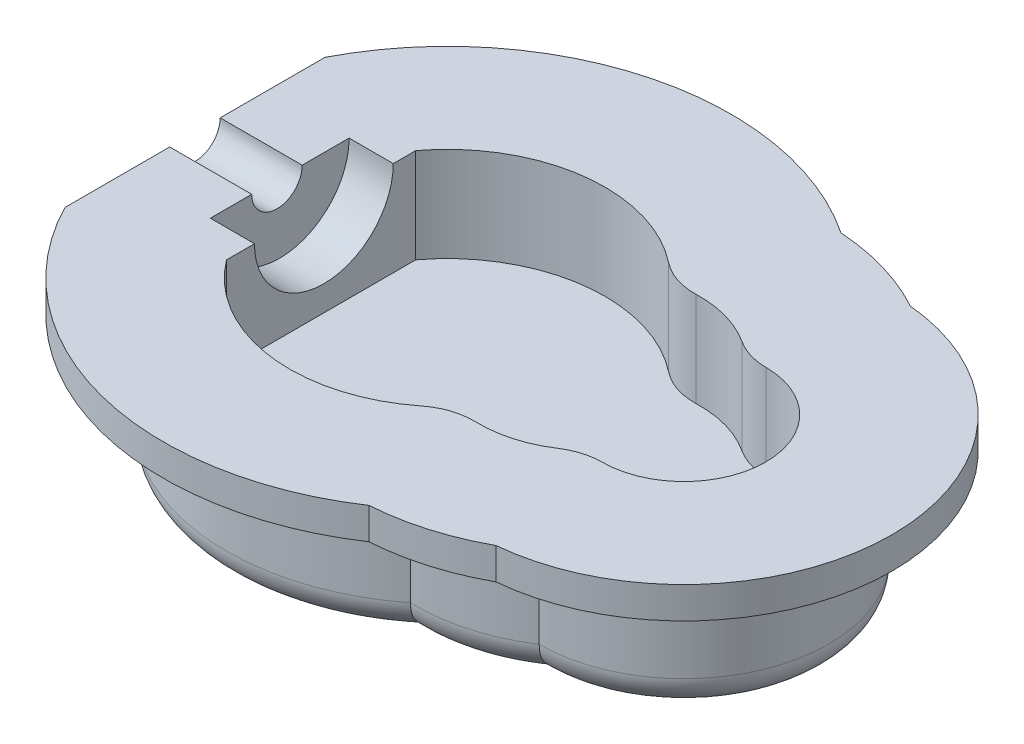
SolidWorks part; units mm, degrees
ref_plane "Front Plane" through (0, 0, 0) normal (0, 0, 1) x (1, 0, 0)
ref_plane "Top Plane" through (0, 0, 0) normal (0, 1, 0) x (1, 0, 0)
ref_plane "Right Plane" through (0, 0, 0) normal (1, 0, 0) x (0, 0, -1)
sketch "Sketch1" plane through (0, 0, 0) normal (0, 1, 0) x (1, 0, 0)
  line L0 (-2125.8372, 0) -> (2252.6955, 0) construction
  line L5 (-57.5, -15) -> (-57.5, 15)
  line L7 (-67.5, -18.0278) -> (-67.5, 18.0278)
  circle A1 centre (0, 0) radius 11
  circle A2 centre (-15, 0) radius 7.5 construction
  circle A3 centre (-37.5, 0) radius 15 construction
  circle A4 centre (0, 0) radius 7.5 construction
  circle A5 centre (-37.5, 0) radius 4
  circle A6 centre (-15, 0) radius 4
  arc A10 (-22.0238, 19.6338) -> (-57.5, 15) centre (-37.5, 0) ccw
  arc A11 (-15.5303, -17.492) -> (-5.4068, -14.6363) centre (-15, 0) ccw
  arc A12 (0.0424, -12.9999) -> (0.0424, 12.9999) centre (0, 0) ccw
  arc A13 (-57.5, -15) -> (-22.0238, -19.6338) centre (-37.5, 0) ccw
  circle A14 centre (-15, 0) radius 17.5 construction
  circle A15 centre (-37.5, 0) radius 25 construction
  circle A16 centre (0, 0) radius 13 construction
  arc A17 (-5.4068, 14.6363) -> (-15.5303, 17.492) centre (-15, 0) ccw
  arc A18 (0.0424, -12.9999) -> (-5.4068, -14.6363) centre (0.075, -22.9999) ccw
  arc A19 (0.0424, 12.9999) -> (-5.4068, 14.6363) centre (0.075, 22.9999) cw
  arc A20 (-15.5303, 17.492) -> (-22.0238, 19.6338) centre (-15.8333, 27.4874) cw
  arc A21 (-15.5303, -17.492) -> (-22.0238, -19.6338) centre (-15.8333, -27.4874) ccw
  arc A31 (0.075, -22.9999) -> (0.075, 22.9999) centre (0, 0) ccw
  arc A32 (0.075, 22.9999) -> (0.075, 22.9999) centre (0.075, 22.9999) cw
  arc A33 (0.075, 22.9999) -> (-15.8333, 27.4874) centre (-15, 0) ccw
  arc A34 (-15.8333, 27.4874) -> (-15.8333, 27.4874) centre (-15.8333, 27.4874) cw
  arc A35 (-15.8333, 27.4874) -> (-67.5, 18.0278) centre (-37.5, 0) ccw
  arc A36 (-67.5, -18.0278) -> (-15.8333, -27.4874) centre (-37.5, 0) ccw
  arc A37 (-15.8333, -27.4874) -> (-15.8333, -27.4874) centre (-15.8333, -27.4874) ccw
  arc A38 (-15.8333, -27.4874) -> (0.075, -22.9999) centre (-15, 0) ccw
  arc A39 (0.075, -22.9999) -> (0.075, -22.9999) centre (0.075, -22.9999) ccw
  point P7 (1088.1233, 0)
  point P9 (919.1687, 0)
  point P19 (991.1425, 0)
  point P22 (1072.1233, 0)
  point P24 (1042.1233, 0)
  point P33 (-2.925, 12.6667)
  dimension "D1" = 30
  dimension "D2" = 22
  dimension "D4" = 15
  dimension "D5" = 15
  dimension "D6" = 8
  dimension "D3" = 8
  dimension "D7" = 10
  dimension "D8" = 10
  dimension "D11" = 10
  dimension "D9" = 2
  dimension "D10" = 30
  dimension "D12" = 10
extrude "Boss-Extrude1" add sketch "Sketch1" along normal blind 10 contours A21 A11 A18 A12 A19 A17 A20 A10 L5 A13 A5 A1 A6 | A5 | A6 | A1 region at (-31.9057, 0, 0) region at (0, 0, 0) region at (-15, 0, 0) region at (-37.5, 0, 0)
extrude "Boss-Extrude2" add sketch "Sketch1<3>" along normal blind 20 contours A36 A11 A21 A13 L5 A10 A20 A17 A19 A12 A18 region at (-66.3559, 0, 0)
sketch "Sketch1<3>" plane through (0, 0, 0) normal (0, 1, 0) x (1, 0, 0) same geometry as "Sketch1"
sketch "Sketch2" plane through (0, 20, 0) normal (0, 1, 0) x (1, 0, 0)
  line L0 (-57.5, -15) -> (-57.5, 15) construction
  line L1 (-57.5, -15) -> (-57.5, 15)
  line L2 (-77.5, -20.6155) -> (-77.5, 20.6155)
  arc A0 (-57.5, -15) -> (-22.0238, -19.6338) centre (-37.5, 0) ccw construction
  arc A1 (-15.5303, -17.492) -> (-22.0238, -19.6338) centre (-15.8333, -27.4874) ccw construction
  arc A2 (-15.5303, -17.492) -> (-5.4068, -14.6363) centre (-15, 0) ccw construction
  arc A3 (0.0424, -12.9999) -> (-5.4068, -14.6363) centre (0.075, -22.9999) ccw construction
  arc A4 (0.0424, -12.9999) -> (0.0424, 12.9999) centre (0, 0) ccw construction
  arc A5 (-5.4068, 14.6363) -> (0.0424, 12.9999) centre (0.075, 22.9999) ccw construction
  arc A6 (-5.4068, 14.6363) -> (-15.5303, 17.492) centre (-15, 0) ccw construction
  arc A7 (-22.0238, 19.6338) -> (-15.5303, 17.492) centre (-15.8333, 27.4874) ccw construction
  arc A8 (-22.0238, 19.6338) -> (-57.5, 15) centre (-37.5, 0) ccw construction
  arc A9 (-57.5, -15) -> (-22.0238, -19.6338) centre (-37.5, 0) ccw
  arc A10 (-15.5303, -17.492) -> (-22.0238, -19.6338) centre (-15.8333, -27.4874) ccw
  arc A11 (-15.5303, -17.492) -> (-5.4068, -14.6363) centre (-15, 0) ccw
  arc A12 (0.0424, -12.9999) -> (-5.4068, -14.6363) centre (0.075, -22.9999) ccw
  arc A13 (0.0424, -12.9999) -> (0.0424, 12.9999) centre (0, 0) ccw
  arc A14 (-5.4068, 14.6363) -> (0.0424, 12.9999) centre (0.075, 22.9999) ccw
  arc A15 (-5.4068, 14.6363) -> (-15.5303, 17.492) centre (-15, 0) ccw
  arc A16 (-22.0238, 19.6338) -> (-15.5303, 17.492) centre (-15.8333, 27.4874) ccw
  arc A17 (-22.0238, 19.6338) -> (-57.5, 15) centre (-37.5, 0) ccw
  arc A18 (-77.5, -20.6155) -> (-12.5, -37.4166) centre (-37.5, 0) ccw
  arc A19 (-12.5, -37.4166) -> (-12.5, -37.4166) centre (-12.5, -37.4166) ccw
  arc A20 (-12.5, -37.4166) -> (3.075, -32.8564) centre (-15, 0) ccw
  arc A21 (3.075, -32.8564) -> (3.075, -32.8564) centre (3.075, -32.8564) ccw
  arc A22 (3.075, -32.8564) -> (3.075, 32.8564) centre (0, 0) ccw
  arc A23 (3.075, 32.8564) -> (3.075, 32.8564) centre (3.075, 32.8564) ccw
  arc A24 (3.075, 32.8564) -> (-12.5, 37.4166) centre (-15, 0) ccw
  arc A25 (-12.5, 37.4166) -> (-12.5, 37.4166) centre (-12.5, 37.4166) ccw
  arc A26 (-12.5, 37.4166) -> (-77.5, 20.6155) centre (-37.5, 0) ccw
  dimension "D1" = 20
extrude "Boss-Extrude3" add sketch "Sketch2" along normal blind 5
sketch "Sketch3" plane through (-77.5, 0, 0) normal (-1, 0, 0) x (0, 0, 1)
  line L0 (-20.6155, 25) -> (20.6155, 25) construction
  circle A0 centre (0, 25) radius 4
  dimension "D1" = 8
sketch "Sketch4" plane through (0, 25, 0) normal (0, 1, 0) x (1, 0, 0)
  line L0 (-77.5, 0) -> (43.4244, 0.8746) construction
  line L1 (-77.5, 4) -> (-77.5, -4) construction
sketch "Sketch5" plane through (0, 0, 0) normal (0, 0, 1) x (1, 0, 0)
  line L0 (-50, 0) -> (-50, 51) construction
  line L1 (-77.5, 25) -> (43.4244, 25) construction
  line L3 (-67.5, 0) -> (-15.8333, 0) construction
  point P2 (-50, 25)
  dimension "D1" = 50
  dimension "D2" = 51
sketch "Sketch6" plane through (-57.5, 0, 0) normal (1, 0, 0) x (0, 0, -1)
  line L0 (0, 25) -> (0.8746, 25) construction
  circle A0 centre (0.4373, 25) radius 11
  dimension "D1" = 22
extrude "Cut-Extrude2" cut sketch "Sketch6" against normal blind 7
extrude "Cut-Extrude3" cut sketch "Sketch3" against normal up to next
fillet "Fillet1" radius 5 6 edges at (-43.8033, 0, 34.4277) (-67.5, 0, 0) (-7.534, 0, -26.4671) (-43.8033, 0, -34.4277) (23, 0, 0) (-7.534, 0, 26.4671)
